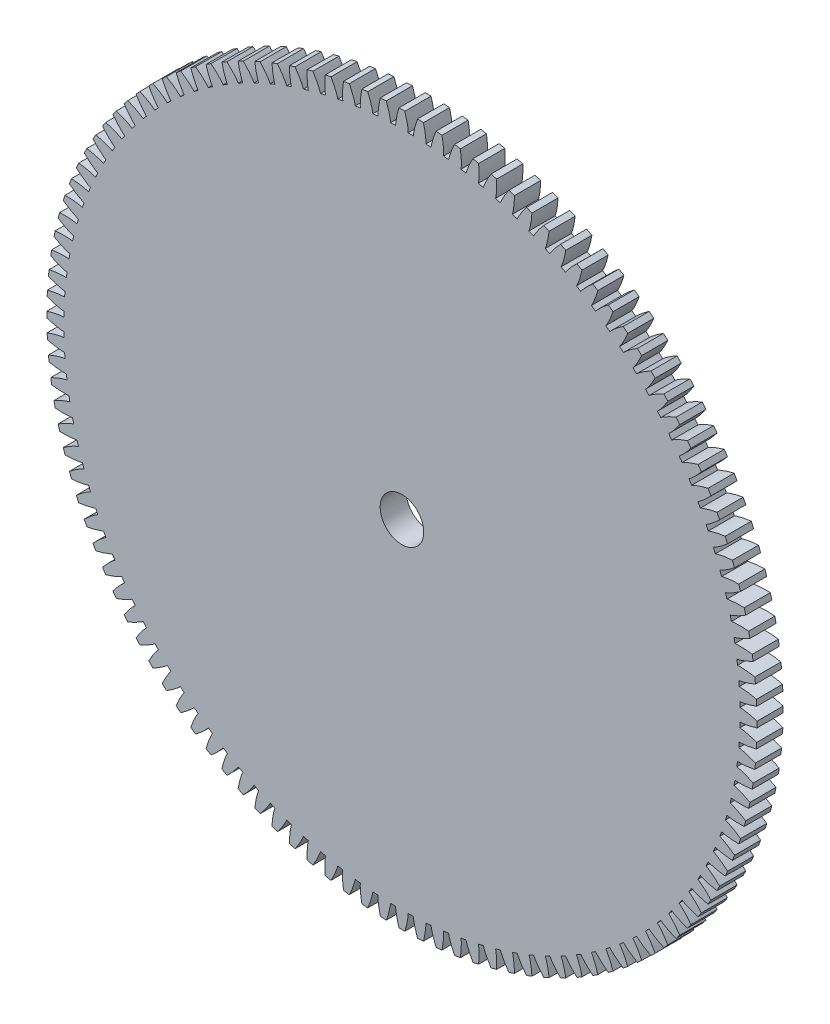
SolidWorks part; units mm, degrees
other "HARMONIC_PMI_surface_bore"
material "Brass"
ref_plane "Front Plane" through (0, 0, 0) normal (0, 0, 1) x (1, 0, 0)
ref_plane "Top Plane" through (0, 0, 0) normal (0, 1, 0) x (1, 0, 0)
ref_plane "Right Plane" through (0, 0, 0) normal (1, 0, 0) x (0, 0, -1)
sketch "Sketch1" plane through (0, 0, 0) normal (0, 0, 1) x (1, 0, 0)
  circle A0 centre (0, 0) radius 40.7737
  dimension "D1" = 81.5474
extrude "Boss-Extrude1" add sketch "Sketch1" along normal blind 3
sketch "Sketch2" plane through (0, 0, 0) normal (0, 0, 1) x (1, 0, 0)
  spline S0 degree 4 poles (38.8211, 0.7235) (38.8293, 0.7236) (38.845, 0.7235) (38.8706, 0.7229) (38.921, 0.7208) (38.9782, 0.7173) (39.0429, 0.7121) (39.1126, 0.7052) (39.1722, 0.6986) (39.2318, 0.6913) (39.2913, 0.6834) (39.3635, 0.673) (39.4502, 0.6596) (39.5519, 0.6423) (39.6675, 0.6208) (39.7857, 0.597) (39.9023, 0.5719) (40.0206, 0.5447) (40.1353, 0.5171) (40.2549, 0.4864) (40.3656, 0.4571) (40.4902, 0.4222) (40.5908, 0.3933) (40.7242, 0.353) (40.8032, 0.3284) (40.8959, 0.2989) (40.9371, 0.2854) (40.9625, 0.277) knots 0 0 0 0 0 0.015084 0.028532 0.04661 0.092111 0.119476 0.146842 0.174209 0.201575 0.228941 0.256307 0.307035 0.361767 0.4165 0.471232 0.525964 0.580697 0.635429 0.690161 0.744894 0.799626 0.854358 0.909091 0.954545 1 1 1 1 1 construction
  spline S1 degree 4 poles (38.8211, 0.7235) (38.8293, 0.7236) (38.845, 0.7235) (38.8706, 0.7229) (38.921, 0.7208) (38.9782, 0.7173) (39.0429, 0.7121) (39.1126, 0.7052) (39.1722, 0.6986) (39.2318, 0.6913) (39.2913, 0.6834) (39.3635, 0.673) (39.4502, 0.6596) (39.5519, 0.6423) (39.6675, 0.6208) (39.7857, 0.597) (39.9023, 0.5719) (40.0206, 0.5447) (40.1353, 0.5171) (40.2549, 0.4864) (40.3656, 0.4571) (40.4902, 0.4222) (40.5908, 0.3933) (40.6953, 0.3617) (40.7462, 0.346) (40.7723, 0.3379) knots 0 0 0 0 0 0.015084 0.028532 0.04661 0.092111 0.119476 0.146842 0.174209 0.201575 0.228941 0.256307 0.307035 0.361767 0.4165 0.471232 0.525964 0.580697 0.635429 0.690161 0.744894 0.799626 0.854358 0.909091 0.909091 0.909091 0.909091 0.909091
  spline S2 degree 4 poles (38.8057, 1.3092) (38.814, 1.3096) (38.8296, 1.3105) (38.8551, 1.3124) (38.9054, 1.3171) (38.9623, 1.3236) (39.0266, 1.3323) (39.0959, 1.3427) (39.1551, 1.3525) (39.2143, 1.3629) (39.2732, 1.3739) (39.3448, 1.388) (39.4307, 1.406) (39.5313, 1.4286) (39.6456, 1.456) (39.7624, 1.486) (39.8776, 1.5172) (39.9942, 1.5505) (40.1074, 1.5841) (40.2252, 1.621) (40.3342, 1.6561) (40.4568, 1.6975) (40.5558, 1.7316) (40.6869, 1.7789) (40.7645, 1.8075) (40.8555, 1.8418) (40.896, 1.8575) (40.9209, 1.8672) knots 0 0 0 0 0 0.015084 0.028532 0.04661 0.092111 0.119476 0.146842 0.174209 0.201575 0.228941 0.256307 0.307035 0.361767 0.4165 0.471232 0.525964 0.580697 0.635429 0.690161 0.744894 0.799626 0.854358 0.909091 0.954545 1 1 1 1 1 construction
  spline S3 degree 4 poles (38.8057, 1.3092) (38.814, 1.3096) (38.8296, 1.3105) (38.8551, 1.3124) (38.9054, 1.3171) (38.9623, 1.3236) (39.0266, 1.3323) (39.0959, 1.3427) (39.1551, 1.3525) (39.2143, 1.3629) (39.2732, 1.3739) (39.3448, 1.388) (39.4307, 1.406) (39.5313, 1.4286) (39.6456, 1.456) (39.7624, 1.486) (39.8776, 1.5172) (39.9942, 1.5505) (40.1074, 1.5841) (40.2252, 1.621) (40.3342, 1.6561) (40.4568, 1.6975) (40.5558, 1.7316) (40.6585, 1.7686) (40.7085, 1.7869) (40.7341, 1.7964) knots 0 0 0 0 0 0.015084 0.028532 0.04661 0.092111 0.119476 0.146842 0.174209 0.201575 0.228941 0.256307 0.307035 0.361767 0.4165 0.471232 0.525964 0.580697 0.635429 0.690161 0.744894 0.799626 0.854358 0.909091 0.909091 0.909091 0.909091 0.909091
  spline S4 degree 1 poles (40.7723, 0.3379) (59.9979, 0.4973) knots 0 0 1 1 construction
  spline S5 degree 1 poles (40.7723, 0.3379) (59.9979, 0.4973) knots 0 0 1 1
  spline S6 degree 4 poles (59.9993, 0.2811) (59.9993, 0.2966) (59.9991, 0.3264) (59.9989, 0.3667) (59.9981, 0.4759) (59.9977, 0.5237) (59.9964, 0.6646) (59.9954, 0.7445) (59.9939, 0.8601) (59.9924, 0.9543) (59.9907, 1.0614) (59.9888, 1.1607) (59.9867, 1.2646) (59.9845, 1.3658) (59.9821, 1.4686) (59.9795, 1.5706) (59.9767, 1.6727) (59.9738, 1.7754) (59.9707, 1.8766) (59.9673, 1.9805) (59.964, 2.0797) (59.9601, 2.1868) (59.9567, 2.2809) (59.9521, 2.3964) (59.949, 2.4763) (59.9429, 2.6171) (59.9408, 2.6648) (59.9359, 2.7739) (59.934, 2.8142) (59.9326, 2.844) (59.9318, 2.8594) knots 0 0 0 0 0 0.020959 0.041918 0.083333 0.123016 0.162698 0.202381 0.242063 0.281746 0.321429 0.361111 0.400794 0.440476 0.480159 0.519841 0.559524 0.599206 0.638889 0.678571 0.718254 0.757937 0.797619 0.837302 0.876984 0.916667 0.958082 0.979041 1 1 1 1 1 construction
  spline S7 degree 4 poles (59.9979, 0.4973) (59.9978, 0.5186) (59.9974, 0.5601) (59.9964, 0.6646) (59.9954, 0.7445) (59.9939, 0.8601) (59.9924, 0.9543) (59.9907, 1.0614) (59.9888, 1.1607) (59.9867, 1.2646) (59.9845, 1.3658) (59.9821, 1.4686) (59.9795, 1.5706) (59.9767, 1.6727) (59.9738, 1.7754) (59.9707, 1.8766) (59.9673, 1.9805) (59.964, 2.0797) (59.9601, 2.1868) (59.9567, 2.2809) (59.9521, 2.3964) (59.949, 2.4763) (59.9445, 2.5807) (59.9427, 2.6222) (59.9417, 2.6435) knots 0.083333 0.083333 0.083333 0.083333 0.083333 0.123016 0.162698 0.202381 0.242063 0.281746 0.321429 0.361111 0.400794 0.440476 0.480159 0.519841 0.559524 0.599206 0.638889 0.678571 0.718254 0.757937 0.797619 0.837302 0.876984 0.916667 0.916667 0.916667 0.916667 0.916667
  spline S8 degree 1 poles (59.9417, 2.6435) (40.7341, 1.7964) knots 0 0 1 1 construction
  spline S9 degree 1 poles (59.9417, 2.6435) (40.7341, 1.7964) knots 0 0 1 1
  spline S10 degree 1 poles (38.8057, 1.3092) (38.8211, 0.7235) knots 0 0 1 1 construction
  spline S11 degree 1 poles (38.8057, 1.3092) (38.8211, 0.7235) knots 0 0 1 1
extrude "Cut-Extrude2" cut sketch "Sketch2" against normal blind 4 and the other way blind 4
ref_axis "Axis1" through (0, 0, -0.15) along (0, 0, 1)
pattern_circular "CirPattern1" count 120 over 360 about axis through (0, 0, -0.15) along (0, 0, 1) of "Cut-Extrude2"
sketch "BoreProfile" plane through (0, 0, 0) normal (0, 0, 1) x (1, 0, 0)
  circle A0 centre (0, 0) radius 2.5
  dimension "BoreDia" = 5
extrude "Bore" cut sketch "BoreProfile" against normal blind 5 and the other way blind 5
ref_axis "Axis2" through (0, 0, -0.15) along (0, 0, 1)
equation "\"FaceWidth\" = 3.0mm"
equation "\"BoreDia\" = 5.0mm"
equation "\"BoreDia@BoreProfile\" = \"BoreDia\""
